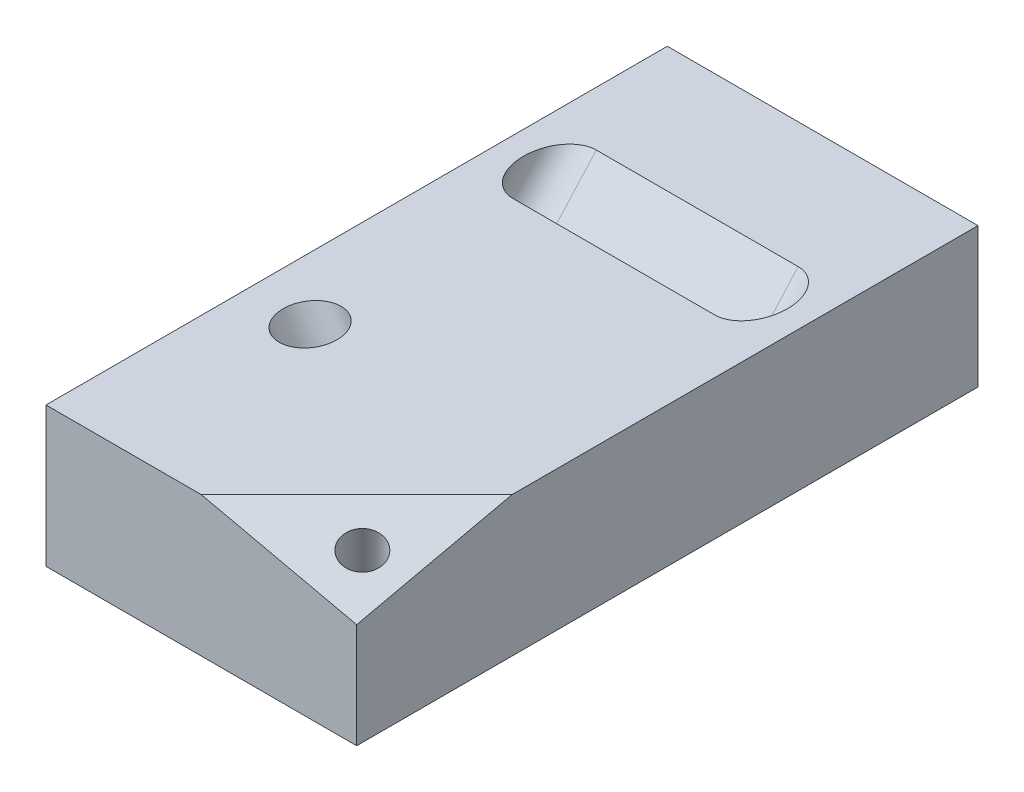
SolidWorks part; units mm, degrees
material "Brass"
ref_plane "Front Plane" through (0, 0, 0) normal (0, 0, 1) x (1, 0, 0)
ref_plane "Top Plane" through (0, 0, 0) normal (0, 1, 0) x (1, 0, 0)
ref_plane "Right Plane" through (0, 0, 0) normal (1, 0, 0) x (0, 0, -1)
sketch "Sketch1" plane through (0, 0, 0) normal (0, 1, 0) x (1, 0, 0)
  line L1 (-100, -200) -> (100, -200)
  line L2 (-100, -200) -> (-100, 200)
  line L3 (-100, 200) -> (100, 200)
  line L4 (100, -200) -> (100, 200)
  line L5 (-100, -200) -> (100, 200) construction
  line L6 (-100, 200) -> (100, -200) construction
  point P0 (0, 0)
  dimension "D1" = 200
  dimension "D2" = 400
extrude "Boss-Extrude1" add sketch "Sketch1" along normal blind 90
sketch "Sketch2" plane through (0, 0, 200) normal (0, 0, 1) x (1, 0, 0)
  line L0 (0, 90) -> (100, 67.5) construction
  line L1 (-100, 90) -> (100, 90) construction
  line L2 (100, 90) -> (100, 0) construction
  dimension "D1" = 100
  dimension "D2" = 22.5
sketch "Sketch3" plane through (100, 0, 0) normal (1, 0, 0) x (0, 0, -1)
  line L0 (-200, 67.5) -> (-100, 90) construction
  line L1 (-200, 90) -> (-200, 0) construction
  line L2 (-200, 90) -> (-200, 67.5) construction
  line L3 (-200, 90) -> (200, 90) construction
  dimension "D1" = 100
ref_plane "Plane1" through (27.5823, 122.588, 27.5823) normal (-0.2144, -0.9529, -0.2144) x (-0.9767, 0.2092, 0.0471)
sketch "Sketch4" plane through (27.5823, 122.588, 27.5823) normal (-0.2144, -0.9529, -0.2144) x (-0.9767, 0.2092, 0.0471)
  line L0 (28.239, -175.3659) -> (-74.1419, -77.8049)
  line L1 (-74.1419, -77.8049) -> (-74.1419, -180.3049)
  line L2 (-74.1419, -180.3049) -> (28.239, -175.3659)
  circle A0 centre (-46.761, -147.8049) radius 12.5
  dimension "D3" = 25
  dimension "D1" = 75
  dimension "D2" = 70
extrude "Cut-Extrude2" cut sketch "Sketch4" against normal through all contours L0 L1 L2
extrude "Cut-Extrude4" cut sketch "Sketch4<3>" along normal through all contours A0
sketch "Sketch4<3>" plane through (27.5823, 122.588, 27.5823) normal (-0.2144, -0.9529, -0.2144) x (-0.9767, 0.2092, 0.0471) same geometry as "Sketch4"
sketch "Sketch9" plane through (0, 90, 0) normal (0, 1, 0) x (1, 0, 0)
  line L0 (-100, -200) -> (0, -200) construction
  line L1 (-100, 200) -> (-100, -200) construction
  point P0 (-60, -70)
  dimension "D1" = 130
  dimension "D2" = 40
ref_plane "Plane2" through (-63.9711, 110.8013, 0) normal (-0.5, 0.866, 0) x (0, 0, 1)
sketch "Sketch10" plane through (-63.9711, 110.8013, 0) normal (-0.5, 0.866, 0) x (0, 0, 1)
  ellipse E0 centre (70, -6.9615) end of major axis (50, -6.9615) minor radius 15
  dimension "D1" = 30
  dimension "D2" = 20
extrude "Cut-Extrude5" cut sketch "Sketch10" against normal blind 100 contours E0
ref_plane "Plane3" through (0, 149.156, -134.3006) normal (0, 0.7431, -0.6691) x (-1, 0, 0)
sketch "Sketch11" plane through (0, 149.156, -134.3006) normal (0, 0.7431, -0.6691) x (-1, 0, 0)
  line L0 (-65, -8.4072) -> (65, -8.4072) construction
  line L1 (-65, 11.5928) -> (65, 11.5928)
  line L2 (-65, -28.4072) -> (65, -28.4072)
  line L3 (100, -88.4072) -> (100, 208.8507) construction
  line L4 (-100, 134.5362) -> (-100, -88.4072) construction
  line L5 (-100, -88.4072) -> (100, -88.4072) construction
  arc A0 (-65, 11.5928) -> (-65, -28.4072) centre (-65, -8.4072) ccw
  arc A1 (65, -28.4072) -> (65, 11.5928) centre (65, -8.4072) ccw
  point P2 (0, -8.4072)
  dimension "D3" = 20
  dimension "D1" = 35
  dimension "D2" = 35
  dimension "D4" = 60
extrude "Cut-Extrude6" cut sketch "Sketch11" against normal through all contours L1 A1 L2 A0
